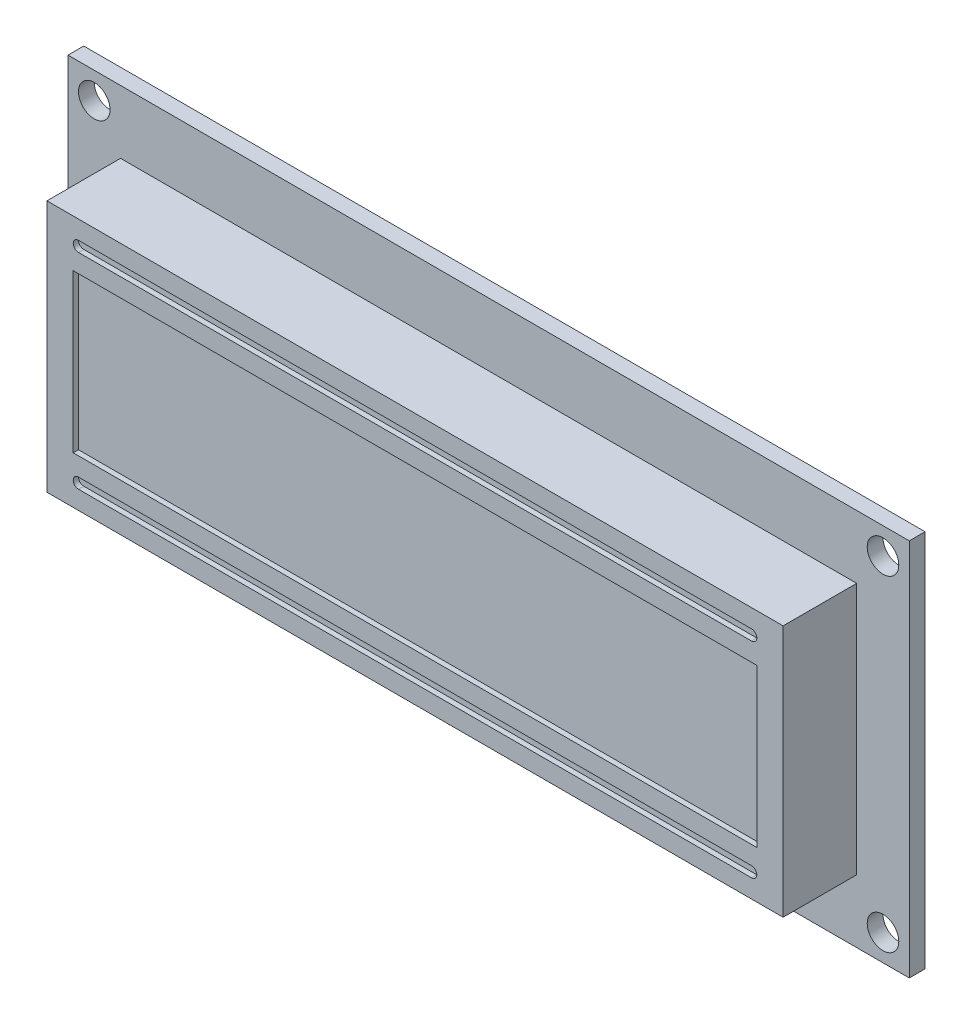
SolidWorks part; units mm, degrees
ref_plane "Front Plane" through (0, 0, 0) normal (0, 0, 1) x (1, 0, 0)
ref_plane "Top Plane" through (0, 0, 0) normal (0, 1, 0) x (1, 0, 0)
ref_plane "Right Plane" through (0, 0, 0) normal (1, 0, 0) x (0, 0, -1)
sketch "Sketch1" plane through (0, 0, 0) normal (0, 0, 1) x (1, 0, 0)
  line L1 (40, -18) -> (-40, -18)
  line L2 (40, -18) -> (40, 18)
  line L3 (40, 18) -> (-40, 18)
  line L4 (-40, -18) -> (-40, 18)
  line L5 (40, -18) -> (-40, 18) construction
  line L6 (40, 18) -> (-40, -18) construction
  point P0 (0, 0)
  dimension "D1" = 80
  dimension "D2" = 36
base flange "Base-Flange1" sketch "Sketch1" thickness 1.5 reverse thickness direction no parameters "D1"=1.2
sketch "Sketch6" plane through (0, 0, 0) normal (0, 0, 1) x (1, 0, 0)
  line L1 (35, -12) -> (-35, -12)
  line L2 (35, -12) -> (35, 12)
  line L3 (35, 12) -> (-35, 12)
  line L4 (-35, -12) -> (-35, 12)
  line L5 (35, -12) -> (-35, 12) construction
  line L6 (35, 12) -> (-35, -12) construction
  point P0 (0, 0)
  dimension "D1" = 24
  dimension "D2" = 70
extrude "Boss-Extrude1" add sketch "Sketch6" along normal blind 7
sketch "Sketch7" plane through (0, 0, 7) normal (0, 0, 1) x (1, 0, 0)
  line L1 (32.5, -7.5) -> (-32.5, -7.5)
  line L2 (32.5, -7.5) -> (32.5, 7.5)
  line L3 (32.5, 7.5) -> (-32.5, 7.5)
  line L4 (-32.5, -7.5) -> (-32.5, 7.5)
  line L5 (32.5, -7.5) -> (-32.5, 7.5) construction
  line L6 (32.5, 7.5) -> (-32.5, -7.5) construction
  point P0 (0, 0)
  dimension "D1" = 15
  dimension "D2" = 65
extrude "Cut-Extrude1" cut sketch "Sketch7" against normal blind 0.5 normal cut yes
sketch "Sketch8" plane through (0, 0, 7) normal (0, 0, 1) x (1, 0, 0)
  line L0 (32, 9.75) -> (-32, 9.75) construction
  line L1 (32, 9.25) -> (-32, 9.25)
  line L2 (32, 10.25) -> (-32, 10.25)
  line L3 (35, 12) -> (-35, 12) construction
  line L4 (-32.5, 0) -> (32.5, 0) construction
  line L5 (-32.5, 7.5) -> (-32.5, -7.5) construction
  line L6 (32.5, -7.5) -> (32.5, 7.5) construction
  line L7 (32, -9.75) -> (-32, -9.75) construction
  line L8 (32, -9.25) -> (-32, -9.25)
  line L9 (32, -10.25) -> (-32, -10.25)
  arc A0 (32, 9.25) -> (32, 10.25) centre (32, 9.75) ccw
  arc A1 (-32, 10.25) -> (-32, 9.25) centre (-32, 9.75) ccw
  arc A2 (32, -9.25) -> (32, -10.25) centre (32, -9.75) cw
  arc A3 (-32, -10.25) -> (-32, -9.25) centre (-32, -9.75) cw
  point P2 (0, 9.75)
  point P18 (0, -9.75)
  dimension "D1" = 64
  dimension "D2" = 1
  dimension "D3" = 2.25
extrude "Cut-Extrude2" cut sketch "Sketch8" against normal blind 0.5 normal cut yes
sketch "Sketch9" plane through (0, 0, -1.5) normal (0, 0, -1) x (-1, 0, 0)
  line L1 (37.5, -15.5) -> (-37.5, -15.5) construction
  line L2 (37.5, -15.5) -> (37.5, 15.5) construction
  line L3 (37.5, 15.5) -> (-37.5, 15.5) construction
  line L4 (-37.5, -15.5) -> (-37.5, 15.5) construction
  line L5 (37.5, -15.5) -> (-37.5, 15.5) construction
  line L6 (37.5, 15.5) -> (-37.5, -15.5) construction
  circle A0 centre (-37.5, 15.5) radius 1.5
  circle A1 centre (-37.5, -15.5) radius 1.5
  circle A2 centre (37.5, 15.5) radius 1.5
  circle A3 centre (37.5, -15.5) radius 1.5
  point P0 (0, 0)
  dimension "D3" = 3
  dimension "D1" = 75
  dimension "D2" = 31
extrude "Cut-Extrude3" cut sketch "Sketch9" against normal up to next normal cut yes
sketch "Bend-Lines1" plane through (0, 0, 0) normal (0, 1, 0) x (1, 0, 0)
sketch "Bounding-Box1" plane through (0, 0, 0) normal (0, 1, 0) x (1, 0, 0)
sheet metal parameters "Sheet-Metal1" thickness 1.5 parameters "D1"=1.2
flat pattern "Flat-Pattern1" [suppressed]
sketch "Bend-Lines2" plane through (0, 0, 0) normal (0, 1, 0) x (1, 0, 0)
sketch "Bounding-Box2" [suppressed] plane through (0, 0, 0) normal (0, 1, 0) x (1, 0, 0)
sheet metal parameters "Sheet-Metal2" thickness 1.5 parameters "D1"=1.2
flat pattern "Flat-Pattern1"
sketch "Bend-Lines2" plane through (0, 0, 0) normal (0, 1, 0) x (1, 0, 0)
sketch "Bounding-Box2" [suppressed] plane through (0, 0, 0) normal (0, 1, 0) x (1, 0, 0)
sheet metal parameters "Sheet-Metal3" thickness 1.5 parameters "D1"=1.2
flat pattern "Flat-Pattern1"
sketch "Bend-Lines2" plane through (0, 0, 0) normal (0, 1, 0) x (1, 0, 0)
sketch "Bounding-Box2" [suppressed] plane through (0, 0, 0) normal (0, 1, 0) x (1, 0, 0)
sheet metal parameters "Sheet-Metal4" thickness 1.5 parameters "D1"=1.2
flat pattern "Flat-Pattern1"
sketch "Bend-Lines2" plane through (0, 0, 0) normal (0, 1, 0) x (1, 0, 0)
sketch "Bounding-Box2" [suppressed] plane through (0, 0, 0) normal (0, 1, 0) x (1, 0, 0)
sheet metal parameters "Sheet-Metal5" thickness 1.5 parameters "D1"=1.2
flat pattern "Flat-Pattern1"
sketch "Bend-Lines2" plane through (0, 0, 0) normal (0, 1, 0) x (1, 0, 0)
sketch "Bounding-Box2" [suppressed] plane through (0, 0, 0) normal (0, 1, 0) x (1, 0, 0)
